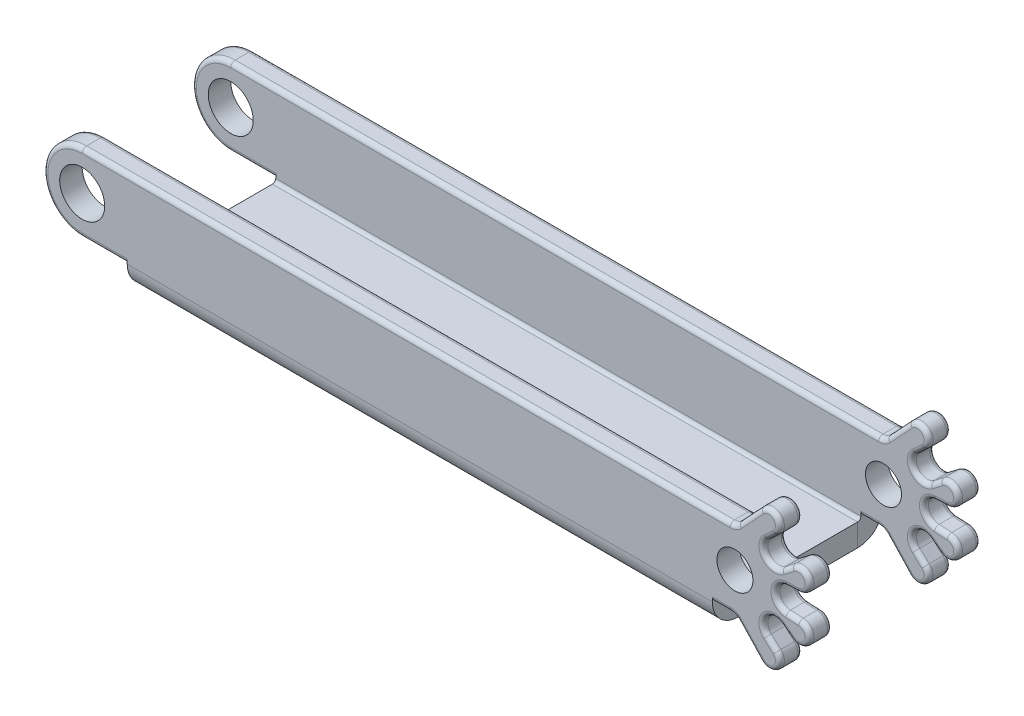
SolidWorks part; units mm, degrees
note: The reader was unsure of these and kept them because the rebuilt part matched: flange length of "Edge-Flange1".
ref_plane "Front Plane" through (0, 0, 0) normal (0, 0, 1) x (1, 0, 0)
ref_plane "Top Plane" through (0, 0, 0) normal (0, 1, 0) x (1, 0, 0)
ref_plane "Right Plane" through (0, 0, 0) normal (1, 0, 0) x (0, 0, -1)
sketch "Sketch1" plane through (0, 0, 0) normal (0, 1, 0) x (1, 0, 0)
  line L1 (-65, 19) -> (65, 19)
  line L2 (-65, 19) -> (-65, -19)
  line L3 (-65, -19) -> (65, -19)
  line L4 (65, 19) -> (65, -19)
  line L5 (-65, 19) -> (65, -19) construction
  line L6 (-65, -19) -> (65, 19) construction
  point P0 (0, 0)
  dimension "D1" = 38
  dimension "D2" = 130
base flange "Base-Flange1" sketch "Sketch1" thickness 5 reverse thickness direction no parameters "D1"=0.7366
edge flange "Edge-Flange1" sketch "Sketch10" flange profiles "Sketch10", "Sketch11" flange angle 90 flange length 23 flange position material inside bend radius 0.7366 thickness 5 parameters "D6"=10, "D8"=1
sketch "Sketch10" plane through (0, 0, 19) normal (0, 0, 1) x (1, 0, 0)
  line L0 (-65, 0) -> (65, 0) construction
  line L1 (-65, 0) -> (65, 0)
  line L2 (-65, 0) -> (-65, 18)
  line L3 (-65, 18) -> (65, 18)
  line L4 (65, 18) -> (65, 0)
sketch "Sketch11" plane through (0, 0, -19) normal (0, 0, -1) x (-1, 0, 0)
  line L0 (-65, 0) -> (65, 0) construction
  line L1 (-65, 0) -> (65, 0)
  line L2 (-65, 0) -> (-65, 18)
  line L3 (-65, 18) -> (65, 18)
  line L4 (65, 18) -> (65, 0)
bend "EdgeBend1" bend radius 0.7366 bend angle 90 parameters "D5"=1
bend "EdgeBend2" bend radius 0.7366 bend angle 90 parameters "D5"=2
sketch "Sketch15" plane through (0, 0, 19) normal (0, 0, 1) x (1, 0, 0)
  line L1 (-65, 18) -> (-65, 0.7366) construction
  line L2 (-75, 18) -> (-65, 18)
  line L3 (-65, 18) -> (-65, 0.7366)
  line L4 (-65, 0.7366) -> (-75, 0.7366)
  arc A0 (-75, 18) -> (-75, 0.7366) centre (-75, 9.3683) ccw
  circle A1 centre (-75, 9.3683) radius 5
  point P8 (-65, 9.3683)
  dimension "D1" = 10
  dimension "D2" = 10
extrude "Boss-Extrude1" add sketch "Sketch15" against normal blind 5 contours A1
mirror "Mirror3" about plane through (0, 0, 0) normal (0, 0, 1) of "Boss-Extrude1"
sketch "Sketch16" plane through (0, 0, 19) normal (0, 0, 1) x (1, 0, 0)
  line L0 (65, 18) -> (70, 18)
  line L1 (70, 9.3683) -> (91.4551, -27.793) construction
  line L2 (70, 9.3683) -> (91.4551, 46.5296) construction
  line L3 (35.0206, 9.3683) -> (142.7481, 9.3683) construction
  line L4 (70, 9.3683) -> (104.0826, -3.0368) construction
  line L5 (70, 9.3683) -> (104.0826, 21.7734) construction
  line L6 (70, 9.3683) -> (94.6256, -11.295) construction
  line L7 (70, 9.3683) -> (87.3049, 23.8889) construction
  line L8 (79.1969, 20.5228) -> (77.1126, 18.5962)
  line L9 (80.3228, 14.7704) -> (82.5821, 16.4885)
  line L10 (81.3802, 11.8654) -> (84.2152, 12.0015)
  line L11 (77.1126, 0.1404) -> (79.1969, -1.7862)
  line L12 (80.3228, 3.9662) -> (82.5821, 2.2481)
  line L13 (81.3802, 6.8712) -> (84.2152, 6.7351)
  line L16 (65, 18) -> (65, 0.7366)
  line L17 (70, 18) -> (75.6742, 24.0664)
  line L18 (65, 0.7366) -> (70, 0.7366)
  line L19 (70, 0.7366) -> (75.6742, -5.3298)
  circle A0 centre (70, 9.3683) radius 17.5 construction
  circle A1 centre (70, 9.3683) radius 14 construction
  circle A2 centre (70, 9.3683) radius 15 construction
  arc A3 (84.2152, 12.0015) -> (82.5821, 16.4885) centre (84.0954, 14.4986) ccw
  arc A4 (79.1969, 20.5228) -> (75.6742, 24.0664) centre (77.5, 22.3587) ccw
  arc A5 (82.5821, 2.2481) -> (84.2152, 6.7351) centre (84.0954, 4.238) ccw
  arc A6 (75.6742, -5.3298) -> (79.1969, -1.7862) centre (77.5, -3.6221) ccw
  circle A7 centre (70, 9.3683) radius 11.5 construction
  arc A8 (77.1126, 18.5962) -> (80.3228, 14.7704) centre (78.8095, 16.7604) ccw
  arc A9 (81.3802, 11.8654) -> (81.3802, 6.8712) centre (81.5, 9.3683) ccw
  arc A10 (80.3228, 3.9662) -> (77.1126, 0.1404) centre (78.8095, 1.9762) ccw
  point P21 (65, 9.3683)
  dimension "D1" = 35
  dimension "D2" = 28
  dimension "D5" = 30
  dimension "D6" = 23
  dimension "D3" = 120
  dimension "D4" = 40
  dimension "D7" = 20
  dimension "D8" = 20
  dimension "D9" = 5
extrude "Boss-Extrude2" add sketch "Sketch16" against normal blind 5
sketch "Sketch17" plane through (0, 0, 19) normal (0, 0, 1) x (1, 0, 0)
  circle A0 centre (70, 9.3683) radius 4
  dimension "D1" = 8
extrude "Cut-Extrude2" cut sketch "Sketch17" against normal blind 5
mirror "Mirror5" about plane through (0, 0, 0) normal (0, 0, 1) of "Cut-Extrude2", "Boss-Extrude2"
fillet "Fillet3" radius 2.5 4 edges at (70, 0.7366, 16.5) (70, 18, 16.5) (70, 0.7366, -16.5) (70, 18, -16.5)
fillet "Fillet4" radius 1 84 edges at (66.9576, 0.7366, 14) (73.2076, 21.4293, 14) (79.273, 24.1212, 14) (78.1548, 19.5595, 14) (76.8944, 15.1534, 14) (81.4525, 15.6295, 14) (86.4446, 15.3537, 14) (82.7977, 11.9335, 14) (79, 9.3683, 14) (82.7977, 6.8031, 14) (86.4446, 3.3829, 14) (81.4525, 3.1071, 14) (76.8944, 3.5832, 14) (78.1548, -0.8229, 14) (79.273, -5.3846, 14) (79.273, -5.3846, 19) (78.1548, -0.8229, 19) (76.8944, 3.5832, 19) (81.4525, 3.1071, 19) (86.4446, 3.3829, 19) (82.7977, 6.8031, 19) (79, 9.3683, 19) (82.7977, 11.9335, 19) (86.4446, 15.3537, 19) (81.4525, 15.6295, 19) (76.8944, 15.1534, 19) (78.1548, 19.5595, 19) (79.273, 24.1212, 19) (73.2076, 21.4293, 19) (66.9576, 0.7366, 19) (79.273, -5.3846, -19) (78.1548, -0.8229, -19) (76.8944, 3.5832, -19) (81.4525, 3.1071, -19) (86.4446, 3.3829, -19) (82.7977, 6.8031, -19) (79, 9.3683, -19) (82.7977, 11.9335, -19) (86.4446, 15.3537, -19) (81.4525, 15.6295, -19) (76.8944, 15.1534, -19) (78.1548, 19.5595, -19) (79.273, 24.1212, -19) (73.2076, 21.4293, -19) (66.9576, 0.7366, -19) (79.273, -5.3846, -14) (78.1548, -0.8229, -14) (76.8944, 3.5832, -14) (81.4525, 3.1071, -14) (86.4446, 3.3829, -14) (82.7977, 6.8031, -14) (79, 9.3683, -14) (82.7977, 11.9335, -14) (86.4446, 15.3537, -14) (81.4525, 15.6295, -14) (76.8944, 15.1534, -14) (78.1548, 19.5595, -14) (79.273, 24.1212, -14) (73.2076, 21.4293, -14) (66.9576, 0.7366, -14) (-3.0424, 18, 14) (-3.0424, 18, 19) (73.2076, -2.6927, 19) (73.2076, -2.6927, 14) (73.2076, -2.6927, -19) (73.2076, -2.6927, -14) (69.9104, 18.2066, 19) (69.9104, 18.2066, 14) (69.9104, 0.53, 19) (69.9104, 0.53, 14) (69.9104, 0.53, -19) (69.9104, 0.53, -14) (69.9104, 18.2066, -19) (69.9104, 18.2066, -14) (-3.0424, 18, -19) (-3.0424, 18, -14) (-70, 0.7366, 14) (-83.6317, 9.3683, 14) (-70, 0.7366, 19) (-83.6317, 9.3683, 19) (-70, 0.7366, -14) (-83.6317, 9.3683, -14) (-70, 0.7366, -19) (-83.6317, 9.3683, -19)
sketch "Bend-Lines1" [suppressed] plane through (0, 0, 0) normal (0, 1, 0) x (1, 0, 0)
sketch "Bounding-Box1" [suppressed] plane through (0, 0, 0) normal (0, 1, 0) x (1, 0, 0)
sheet metal parameters "Sheet-Metal1" thickness 5 parameters "D1"=0.7366
flat pattern "Flat-Pattern1" [suppressed]
sketch "Bend-Lines2" plane through (0, 0, 0) normal (0, 1, 0) x (1, 0, 0)
sketch3d "Bounding-Box2" [suppressed]
  line L0 (-72.5, -19, 0) -> (72.5, -19, 0) construction
  line L1 (-72.5, 19, 0) -> (72.5, 19, 0) construction
  line L2 (-72.5, -19, 0) -> (-72.5, 19, 0) construction
  line L3 (72.5, -19, 0) -> (72.5, 19, 0) construction
sheet metal parameters "Sheet-Metal2" thickness 5 parameters "D1"=0.7366
flat pattern "Flat-Pattern1"
sketch "Bend-Lines2" plane through (0, 0, 0) normal (0, 1, 0) x (1, 0, 0)
  line L0 (72.5, 15.8054) -> (-72.5, 15.8054) construction
  line L1 (-72.5, -15.8054) -> (72.5, -15.8054) construction
  line L2 (72.5, 15.8054) -> (-72.5, 15.8054) construction
  line L3 (-72.5, -15.8054) -> (72.5, -15.8054) construction
sketch3d "Bounding-Box2" [suppressed]
  line L0 (72.5, -35.6108, 0) -> (-72.5, -35.6108, 0) construction
  line L1 (72.5, 35.6108, 0) -> (-72.5, 35.6108, 0) construction
  line L2 (72.5, -35.6108, 0) -> (72.5, 35.6108, 0) construction
  line L3 (-72.5, -35.6108, 0) -> (-72.5, 35.6108, 0) construction
bend of the flat pattern "Flatten-<EdgeBend1>1"
bend of the flat pattern "Flatten-<EdgeBend2>1"
sheet metal parameters "Sheet-Metal3" thickness 5 parameters "D1"=0.7366
flat pattern "Flat-Pattern1"
sketch "Bend-Lines2" plane through (0, 0, 0) normal (0, 1, 0) x (1, 0, 0)
  line L0 (67.5, 15.8054) -> (-67.5, 15.8054) construction
  line L1 (-67.5, -15.8054) -> (67.5, -15.8054) construction
  line L2 (67.5, 15.8054) -> (-67.5, 15.8054) construction
  line L3 (-67.5, -15.8054) -> (67.5, -15.8054) construction
sketch3d "Bounding-Box2" [suppressed]
  line L0 (-86.1316, -35.6108, 0) -> (67.5, -35.6108, 0) construction
  line L1 (-86.1316, 35.6108, 0) -> (67.5, 35.6108, 0) construction
  line L2 (-86.1316, -35.6108, 0) -> (-86.1316, 35.6108, 0) construction
  line L3 (67.5, -35.6108, 0) -> (67.5, 35.6108, 0) construction
bend of the flat pattern "Flatten-<EdgeBend1>1"
bend of the flat pattern "Flatten-<EdgeBend2>1"
sheet metal parameters "Sheet-Metal7" thickness 5 parameters "D1"=0.7366
flat pattern "Flat-Pattern1"
sketch "Bend-Lines2" plane through (0, 0, 0) normal (0, 1, 0) x (1, 0, 0)
  line L0 (67.5, 15.8054) -> (-67.5, 15.8054) construction
  line L1 (-67.5, -15.8054) -> (67.5, -15.8054) construction
  line L2 (67.5, 15.8054) -> (-67.5, 15.8054) construction
  line L3 (-67.5, -15.8054) -> (67.5, -15.8054) construction
sketch3d "Bounding-Box2" [suppressed]
  line L0 (-86.1316, -35.6108, 0) -> (67.5, -35.6108, 0) construction
  line L1 (-86.1316, 35.6108, 0) -> (67.5, 35.6108, 0) construction
  line L2 (-86.1316, -35.6108, 0) -> (-86.1316, 35.6108, 0) construction
  line L3 (67.5, -35.6108, 0) -> (67.5, 35.6108, 0) construction
bend of the flat pattern "Flatten-<EdgeBend1>1"
bend of the flat pattern "Flatten-<EdgeBend2>1"
sheet metal parameters "Sheet-Metal8" thickness 5 parameters "D1"=0.7366
flat pattern "Flat-Pattern1"
sketch "Bend-Lines2" plane through (0, 0, 0) normal (0, 1, 0) x (1, 0, 0)
  line L0 (67.5, 15.8054) -> (-67.5, 15.8054) construction
  line L1 (-67.5, -15.8054) -> (67.5, -15.8054) construction
  line L2 (67.5, 15.8054) -> (-67.5, 15.8054) construction
  line L3 (-67.5, -15.8054) -> (67.5, -15.8054) construction
sketch3d "Bounding-Box2" [suppressed]
  line L0 (-86.1316, -42.4695, 0) -> (84.0954, -42.4695, 0) construction
  line L1 (-86.1316, 35.6108, 0) -> (84.0954, 35.6108, 0) construction
  line L2 (-86.1316, -42.4695, 0) -> (-86.1316, 35.6108, 0) construction
  line L3 (84.0954, -42.4695, 0) -> (84.0954, 35.6108, 0) construction
bend of the flat pattern "Flatten-<EdgeBend1>1"
bend of the flat pattern "Flatten-<EdgeBend2>1"
sheet metal parameters "Sheet-Metal9" thickness 5 parameters "D1"=0.7366
flat pattern "Flat-Pattern1"
sketch "Bend-Lines2" plane through (0, 0, 0) normal (0, 1, 0) x (1, 0, 0)
  line L0 (67.5, 15.8054) -> (-67.5, 15.8054) construction
  line L1 (-67.5, -15.8054) -> (67.5, -15.8054) construction
  line L2 (67.5, 15.8054) -> (-67.5, 15.8054) construction
  line L3 (-67.5, -15.8054) -> (67.5, -15.8054) construction
sketch3d "Bounding-Box2" [suppressed]
  line L0 (-86.1316, -42.4695, 0) -> (84.0954, -42.4695, 0) construction
  line L1 (-86.1316, 35.6108, 0) -> (84.0954, 35.6108, 0) construction
  line L2 (-86.1316, -42.4695, 0) -> (-86.1316, 35.6108, 0) construction
  line L3 (84.0954, -42.4695, 0) -> (84.0954, 35.6108, 0) construction
bend of the flat pattern "Flatten-<EdgeBend1>1"
bend of the flat pattern "Flatten-<EdgeBend2>1"
sheet metal parameters "Sheet-Metal10" thickness 5 parameters "D1"=0.7366
flat pattern "Flat-Pattern1"
sketch "Bend-Lines2" plane through (0, 0, 0) normal (0, 1, 0) x (1, 0, 0)
  line L0 (65, 15.8054) -> (-65, 15.8054) construction
  line L1 (-65, -15.8054) -> (65, -15.8054) construction
  line L2 (65, 15.8054) -> (-65, 15.8054) construction
  line L3 (-65, -15.8054) -> (65, -15.8054) construction
sketch3d "Bounding-Box2" [suppressed]
  line L0 (-83.6317, -42.4695, 0) -> (86.5954, -42.4695, 0) construction
  line L1 (-83.6317, 42.4695, 0) -> (86.5954, 42.4695, 0) construction
  line L2 (-83.6317, -42.4695, 0) -> (-83.6317, 42.4695, 0) construction
  line L3 (86.5954, -42.4695, 0) -> (86.5954, 42.4695, 0) construction
bend of the flat pattern "Flatten-<EdgeBend1>1"
bend of the flat pattern "Flatten-<EdgeBend2>1"
